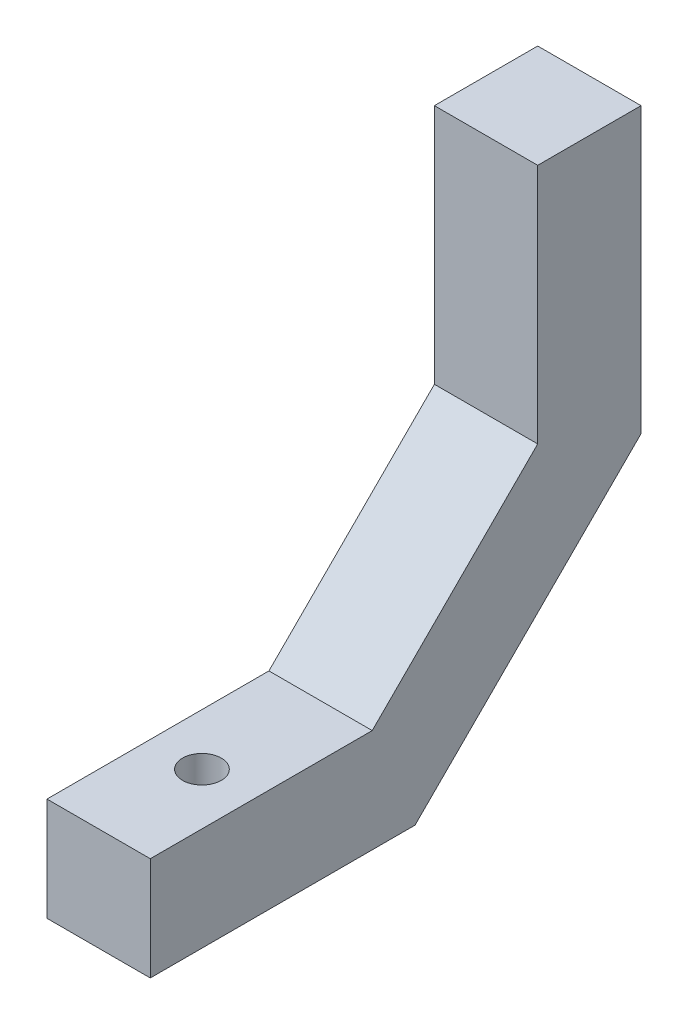
SolidWorks part; units mm, degrees
ref_plane "Front Plane" through (0, 0, 0) normal (0, 0, 1) x (1, 0, 0)
ref_plane "Top Plane" through (0, 0, 0) normal (0, 1, 0) x (1, 0, 0)
ref_plane "Right Plane" through (0, 0, 0) normal (1, 0, 0) x (0, 0, -1)
ref_axis "Z" through (0, 0, 39.9) along (0, 0, -1)
sketch "Sketch1" plane through (0, 0, 0) normal (1, 0, 0) x (0, 0, -1)
  line L0 (-8, 4) -> (0, 4)
  line L1 (0, 4) -> (0, -18)
  line L2 (0, -18) -> (-17.5, -35.5)
  line L3 (-17.5, -35.5) -> (-30, -35.5)
  line L4 (-30, -35.5) -> (-30, -27.5) construction
  line L5 (-30, -27.5) -> (-20.8137, -27.5)
  line L6 (-20.8137, -27.5) -> (-8, -14.6863)
  line L7 (-8, -14.6863) -> (-8, 4)
  line L8 (-13.4134, -20.0997) -> (-7.7566, -25.7566) construction
  line L10 (-30, -27.5) -> (-38, -27.5)
  line L11 (-30, -27.5) -> (-30, -35.5) construction
  line L12 (-30, -35.5) -> (-38, -35.5)
  line L13 (-38, -27.5) -> (-38, -35.5)
  dimension "D1" = 8
  dimension "D2" = 30
  dimension "D3" = 35.5
  dimension "D4" = 4
  dimension "D5" = 135
  dimension "D6" = 17.5
  dimension "D7" = 8
extrude "Boss-Extrude1" add sketch "Sketch1" along normal blind 4 and the other way blind 4
sketch "Sketch3" plane through (0, -27.5, 0) normal (0, 1, 0) x (1, 0, 0)
  line L0 (-4.4, 0) -> (4.4, 0) construction
  line L1 (0, -19.8) -> (0, 19.8) construction
  circle A0 centre (0, -30) radius 1.5
  dimension "D2" = 3
  dimension "D1" = 30
extrude "Cut-Extrude1" cut sketch "Sketch3" against normal through all
ref_axis "Axis1" through (0, -27.5, 30) along (0, 1, 0)
equation "\"rbracket-width\"= 8"
equation "\"D1@Boss-Extrude1\"=\"rbracket-width\"/2"
equation "\"D2@Boss-Extrude1\"=\"rbracket-width\"/2"
equation "\"EyeCaptureRadius\"= ( \"EyeDiameter\" + \"EyeClearance\" ) / 2"
equation "\"rbracket_planetocenterline_dist\"= \"BasePlaneDistance\""
equation "\"D2@Sketch1\"=\"rbracket_planetocenterline_dist\""
equation "\"EyeDiameter\" = 35"
equation "\"BasePlaneDistance\" = 30"
equation "\"EyeClearance\" = 2"
equation "\"D1@Sketch1\"=\"rbracket-width\""
equation "\"D3@Sketch1\"=(\"EyeDiameter\"+\"EyeClearance\"+\"EyeClearance\")/2 + \"L2Thickness\" + \"rbracket-width\""
equation "\"D4@Sketch1\"=\"rbracket-width\"/2"
equation "\"D6@Sketch1\"=\"EyeDiameter\"/2"
equation "\"D7@Sketch1\"=\"rbracket-width\""
equation "\"D1@Sketch3\"=\"BasePlaneDistance\""
equation "\"L2Thickness\" = 8"
